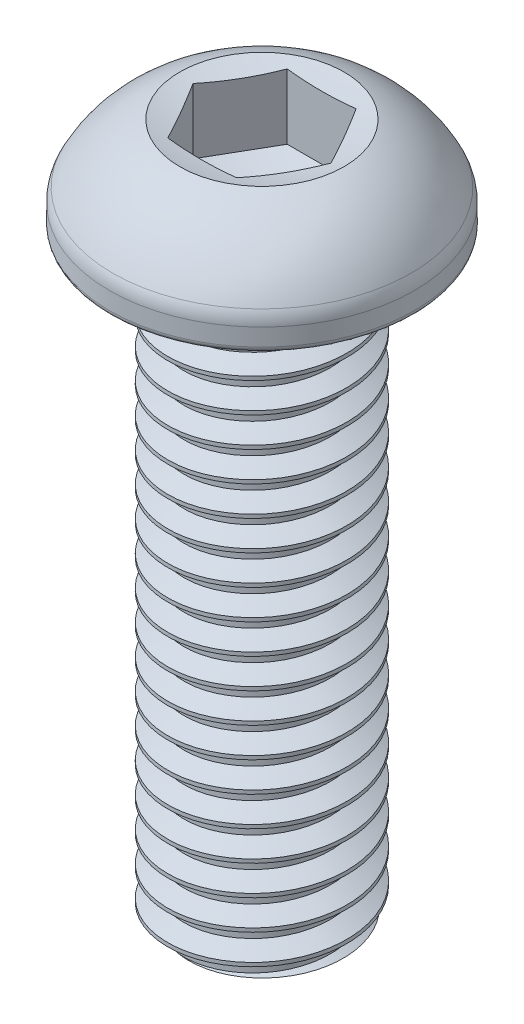
SolidWorks part; units mm, degrees
material "304 STAINLESS STEEL"
ref_plane "Front Plane" through (0, 0, 0) normal (0, 0, 1) x (1, 0, 0)
ref_plane "Top Plane" through (0, 0, 0) normal (0, 1, 0) x (1, 0, 0)
ref_plane "Right Plane" through (0, 0, 0) normal (1, 0, 0) x (0, 0, -1)
ref_axis "X-Axis" through (-88.99, 0, 0) along (1, 0, 0)
ref_axis "Y-Axis" through (0, 55, 0) along (0, -1, 0)
ref_axis "Z-Axis" through (0, 0, -88.99) along (0, 0, 1)
sketch "Sketch1" plane through (0, 0, 0) normal (0, 0, 1) x (1, 0, 0)
  line L0 (0, 0) -> (5.1, 0)
  line L1 (5.1, 0) -> (5.1, 1)
  line L2 (0, 0) -> (0, 3.2)
  line L3 (0, 3.2) -> (2.75, 3.2)
  arc A0 (2.75, 3.2) -> (5.1, 1) centre (1.4224, -0.5733) cw
  dimension "D5" = 4
  dimension "D1" = 5.1
  dimension "D2" = 3.2
  dimension "D3" = 2.75
  dimension "D4" = 1
revolve "Revolve1" add sketch "Sketch1" angle 360 about axis through (0, 55, 0) along (0, -1, 0)
fillet "Fillet1" radius 0.2 1 edges at (0, 0, 5.1)
fillet "Fillet2" radius 1 1 edges at (0, 1, 5.1)
sketch "Sketch2" plane through (0, 0, 0) normal (0, -1, 0) x (1, 0, 0)
  circle A0 centre (0, 0) radius 3
  dimension "D1" = 6
extrude "Boss-Extrude1" add sketch "Sketch2" along normal blind 20
thread "Thread1" pitch 1 method cut profile "Thread Profile1" start angle 0, offset 2, length 0, pitch 1, diameter 6
ref_plane "Plane1" through (3, -22, 0) normal (0, 0, 1) x (1, 0, 0)
sketch "Thread Profile1" plane through (3, -22, 0) normal (0, 0, 1) x (1, 0, 0)
  line L0 (0, 0) -> (0, 1) construction
  line L11 (0, 0) -> (0, 0.875)
  line L12 (0, 0.875) -> (-0.5413, 0.5625)
  line L13 (-0.5413, 0.5625) -> (-0.5413, 0.3125)
  line L15 (-0.5413, 0.3125) -> (0, 0)
  line L17 (-0.5413, 0.4375) -> (0, 0.4375) construction
  point P2 (0, 0)
  dimension "Pitch" = 1
  dimension "Profile_Angle" = 60
  dimension "Profile_Land" = 0.25
  dimension "Profile_Height" = 0.5413
sketch "Sketch6" plane through (0, 0, 0) normal (0, 0, 1) x (1, 0, 0)
  line L0 (0, 0) -> (0, 3.2)
  line L1 (2.75, 3.2) -> (-2.75, 3.2) construction
  line L2 (0, 3.2) -> (2.75, 3.2)
  line L3 (0, 0) -> (4.9, 0)
  line L4 (4.9, 0) -> (2.75, 3.2)
  arc A0 (4.9925, 1.2306) -> (2.75, 3.2) centre (1.4224, -0.5733) ccw construction
revolve "Revolve2" add sketch "Sketch6" angle 360 about axis through (0, 55, 0) along (0, -1, 0)
sketch "Sketch7" plane through (0, 3.2, 0) normal (0, 1, 0) x (1, 0, 0)
  line L1 (1.1547, -2) -> (2.3094, 0)
  line L2 (2.3094, 0) -> (1.1547, 2)
  line L3 (1.1547, 2) -> (-1.1547, 2)
  line L4 (-1.1547, 2) -> (-2.3094, 0)
  line L5 (-2.3094, 0) -> (-1.1547, -2)
  line L6 (-1.1547, -2) -> (1.1547, -2)
  circle A0 centre (0, 0) radius 2 construction
  dimension "D1" = 4
extrude "Cut-Extrude1" cut sketch "Sketch7" against normal blind 2.3
sketch "Sketch8" plane through (0, 0, 0) normal (0, 0, 1) x (1, 0, 0)
  line L0 (0, 0.9) -> (0, 0.5)
  line L1 (0, 0.9) -> (2.3094, 0.9)
  line L2 (1.1547, 0.9) -> (-1.1547, 0.9) construction
  line L3 (1.1547, 0.9) -> (-1.1547, 0.9) construction
  line L4 (-2.3094, 0.9) -> (-2.3094, 3.2) construction
  line L5 (-2.3094, 0.9) -> (-2.3094, 3.2) construction
  line L6 (2.3094, 0.9) -> (2.3094, 3.2) construction
  line L7 (2.3094, 0.9) -> (2.3094, 3.2) construction
  line L8 (0, 0.5) -> (0.25, 0.5)
  arc A1 (0.25, 0.5) -> (2.3094, 0.9) centre (0.25, 6.0014) ccw
  dimension "D2" = 0.25
  dimension "D1" = 0.4
revolve "Cut-Revolve1" cut sketch "Sketch8" angle 360 about axis through (0, 55, 0) along (0, -1, 0)
sketch "Sketch9" plane through (0, 0, 0) normal (0, 0, 1) x (1, 0, 0)
  line L0 (2.75, 3.2) -> (-2.75, 3.2) construction
  line L1 (2.75, 3.2) -> (-2.75, 3.2)
  line L2 (0, 3.2) -> (0, 2.8144)
  line L3 (0, 2.8144) -> (-2.75, 2.8144) construction
  arc A0 (2.75, 3.2) -> (0, 2.8144) centre (0, 12.8144) cw
  dimension "D1" = 10
revolve "Cut-Revolve2" cut sketch "Sketch9" angle 360 about axis through (0, 55, 0) along (0, -1, 0) region at (1.034, 3.0455, 0)
sketch "Sketch10" plane through (0, 0, 0) normal (0, 0, 1) x (1, 0, 0)
  line L0 (3, -19.6) -> (3, -20)
  line L1 (3, -20) -> (2.4, -20)
  line L2 (2.4, -20) -> (3, -19.6)
  line L3 (-2.2716, -20) -> (2.1213, -20) construction
  line L4 (3, -19.125) -> (3, -19) construction
  dimension "D1" = 0.4
  dimension "D2" = 0.6
revolve "Cut-Revolve3" cut sketch "Sketch10" angle 360 about axis through (0, 55, 0) along (0, -1, 0)
